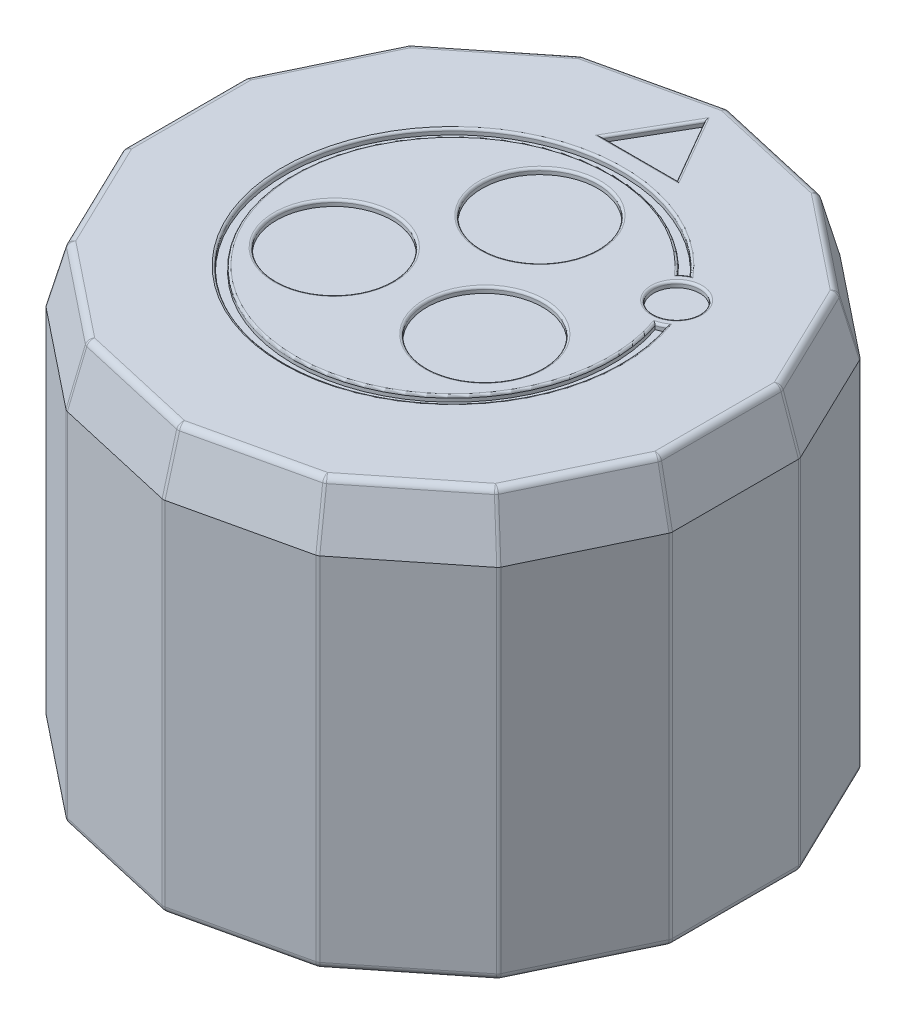
SolidWorks part; units mm, degrees
ref_plane "Front Plane" through (0, 0, 0) normal (0, 0, 1) x (1, 0, 0)
ref_plane "Top Plane" through (0, 0, 0) normal (0, 1, 0) x (1, 0, 0)
ref_plane "Right Plane" through (0, 0, 0) normal (1, 0, 0) x (0, 0, -1)
sketch "Sketch2" plane through (0, 0, 0) normal (0, 1, 0) x (1, 0, 0)
  line L1 (5.5103, -11.4423) -> (9.9293, -7.9183)
  line L2 (9.9293, -7.9183) -> (12.3816, -2.826)
  line L3 (12.3816, -2.826) -> (12.3816, 2.826)
  line L4 (12.3816, 2.826) -> (9.9293, 7.9183)
  line L5 (9.9293, 7.9183) -> (5.5103, 11.4423)
  line L6 (5.5103, 11.4423) -> (0, 12.7)
  line L7 (0, 12.7) -> (-5.5103, 11.4423)
  line L8 (-5.5103, 11.4423) -> (-9.9293, 7.9183)
  line L9 (-9.9293, 7.9183) -> (-12.3816, 2.826)
  line L10 (-12.3816, 2.826) -> (-12.3816, -2.826)
  line L11 (-12.3816, -2.826) -> (-9.9293, -7.9183)
  line L12 (-9.9293, -7.9183) -> (-5.5103, -11.4423)
  line L13 (-5.5103, -11.4423) -> (0, -12.7)
  line L14 (0, -12.7) -> (5.5103, -11.4423)
  circle A0 centre (0, 0) radius 12.7 construction
  dimension "D1" = 25.4
extrude "Boss-Extrude2" add sketch "Sketch2" along normal blind 2.54 draft 15
sketch "Sketch3" plane through (0, 0, 0) normal (0, -1, 0) x (1, 0, 0)
  line L0 (0, 10.0947) -> (-4.3799, 9.095)
  line L1 (0, 12.7) -> (-5.5103, 11.4423)
  line L2 (-5.5103, 11.4423) -> (-9.9293, 7.9183)
  line L3 (-9.9293, 7.9183) -> (-12.3816, 2.826)
  line L4 (-12.3816, 2.826) -> (-12.3816, -2.826)
  line L5 (-12.3816, -2.826) -> (-9.9293, -7.9183)
  line L6 (-9.9293, -7.9183) -> (-5.5103, -11.4423)
  line L7 (-5.5103, -11.4423) -> (0, -12.7)
  line L8 (0, -12.7) -> (5.5103, -11.4423)
  line L9 (5.5103, -11.4423) -> (9.9293, -7.9183)
  line L10 (9.9293, -7.9183) -> (12.3816, -2.826)
  line L11 (12.3816, -2.826) -> (12.3816, 2.826)
  line L12 (12.3816, 2.826) -> (9.9293, 7.9183)
  line L13 (9.9293, 7.9183) -> (5.5103, 11.4423)
  line L14 (5.5103, 11.4423) -> (0, 12.7)
  line L15 (-4.3799, 9.095) -> (-7.8923, 6.2939)
  line L16 (-7.8923, 6.2939) -> (-9.8416, 2.2463)
  line L17 (-9.8416, 2.2463) -> (-9.8416, -2.2463)
  line L18 (-9.8416, -2.2463) -> (-7.8923, -6.2939)
  line L19 (-7.8923, -6.2939) -> (-4.3799, -9.095)
  line L20 (-4.3799, -9.095) -> (0, -10.0947)
  line L21 (0, -10.0947) -> (4.3799, -9.095)
  line L22 (4.3799, -9.095) -> (7.8923, -6.2939)
  line L23 (7.8923, -6.2939) -> (9.8416, -2.2463)
  line L24 (9.8416, -2.2463) -> (9.8416, 2.2463)
  line L25 (9.8416, 2.2463) -> (7.8923, 6.2939)
  line L26 (7.8923, 6.2939) -> (4.3799, 9.095)
  line L27 (4.3799, 9.095) -> (0, 10.0947)
  line L28 (0, 0) -> (0, 3.7295) construction
  line L29 (0, 0) -> (-2.7063, -1.5625) construction
  line L30 (1.4494, 2.6266) -> (-2.9994, 0.0581)
  line L33 (-12.3816, -2.826) -> (-12.3816, 2.826) construction
  circle A0 centre (0, 0) radius 12.7 construction
  circle A1 centre (0, 0) radius 3 construction
  circle A2 centre (0, 0) radius 5.08
  circle A3 centre (0, 0) radius 3
  line M29 (5.5103, 11.4423) -> (0, 12.7)
  line M30 (0, 12.7) -> (-5.5103, 11.4423)
  line M31 (-5.5103, 11.4423) -> (-9.9293, 7.9183)
  line M32 (-9.9293, 7.9183) -> (-12.3816, 2.826)
  line M33 (-12.3816, 2.826) -> (-12.3816, -2.826)
  line M34 (-12.3816, -2.826) -> (-9.9293, -7.9183)
  line M35 (-9.9293, -7.9183) -> (-5.5103, -11.4423)
  line M36 (-5.5103, -11.4423) -> (0, -12.7)
  line M37 (0, -12.7) -> (5.5103, -11.4423)
  line M38 (5.5103, -11.4423) -> (9.9293, -7.9183)
  line M39 (9.9293, -7.9183) -> (12.3816, -2.826)
  line M40 (12.3816, -2.826) -> (12.3816, 2.826)
  line M41 (12.3816, 2.826) -> (9.9293, 7.9183)
  line M42 (9.9293, 7.9183) -> (5.5103, 11.4423)
  dimension "D1" = 25.4
  dimension "D3" = 6
  dimension "D4" = 60
  dimension "D6" = 10.16
  dimension "D5" = 1.55
  dimension "D2" = 2.54
extrude "Boss-Extrude3" add sketch "Sketch3" along normal blind 15.73 contours A2 A1 | L27 L26 L25 L24 L23 L22 L21 L20 L19 L18 L17 L16 L15 L0 M42 M29 M30 M31 M32 M33 M34 M35 M36 M37 M38 M39 M40 M41
sketch "Sketch5" plane through (0, 0, 0) normal (0, -1, 0) x (1, 0, 0)
  circle A0 centre (0, 0) radius 3.125
  dimension "D1" = 6.25
extrude "Cut-Extrude1" cut sketch "Sketch5" against normal blind 1.27
fillet "Fillet1" radius 1.905 15 edges at (0, 0, 5.08) (8.867, 0, 4.2701) (9.8416, 0, 0) (8.867, 0, -4.2701) (6.1361, 0, -7.6945) (2.19, 0, -9.5948) (-2.19, 0, -9.5948) (-6.1361, 0, -7.6945) (-8.867, 0, -4.2701) (-9.8416, 0, 0) (-8.867, 0, 4.2701) (-6.1361, 0, 7.6945) (-2.19, 0, 9.5948) (2.19, 0, 9.5948) (6.1361, 0, 7.6945)
fillet "Fillet2" radius 0.25 2 edges at (0, -15.73, -5.08) (0, -15.73, -3)
fillet "Fillet6" radius 0.3 42 edges at (10.5422, 2.54, 5.0769) (11.701, 2.54, 0) (10.5422, 2.54, -5.0769) (7.2955, 2.54, -9.1482) (2.6037, 2.54, -11.4076) (0, 1.27, 12.351) (-5.3589, 1.27, 11.1278) (-9.6564, 1.27, 7.7007) (-12.0413, 1.27, 2.7483) (-12.0413, 1.27, -2.7483) (-9.6564, 1.27, -7.7007) (-5.3589, 1.27, -11.1278) (0, 1.27, -12.351) (5.3589, 1.27, -11.1278) (9.6564, 1.27, -7.7007) (12.0413, 1.27, -2.7483) (12.0413, 1.27, 2.7483) (9.6564, 1.27, 7.7007) (5.3589, 1.27, 11.1278) (-2.6037, 2.54, -11.4076) (-7.2955, 2.54, -9.1482) (-10.5422, 2.54, -5.0769) (-11.701, 2.54, 0) (-10.5422, 2.54, 5.0769) (2.6037, 2.54, 11.4076) (-7.2955, 2.54, 9.1482) (-2.6037, 2.54, 11.4076) (9.9293, -7.865, 7.9183) (5.5103, -7.865, 11.4423) (0, -7.865, 12.7) (-5.5103, -7.865, 11.4423) (-9.9293, -7.865, 7.9183) (-12.3816, -7.865, 2.826) (-12.3816, -7.865, -2.826) (-9.9293, -7.865, -7.9183) (-5.5103, -7.865, -11.4423) (0, -7.865, -12.7) (5.5103, -7.865, -11.4423) (9.9293, -7.865, -7.9183) (12.3816, -7.865, -2.826) (7.2955, 2.54, 9.1482) (12.3816, -7.865, 2.826)
fillet "Fillet7" radius 0.3 42 edges at (-5.507, -15.73, 11.4354) (-2.7552, -15.73, 12.0712) (0, -15.73, 12.6923) (2.7552, -15.73, 12.0712) (5.507, -15.73, 11.4354) (7.7198, -15.73, 9.6803) (9.9232, -15.73, 7.9135) (11.1554, -15.73, 5.3722) (12.3741, -15.73, 2.8243) (12.3816, -15.73, 0) (12.3741, -15.73, -2.8243) (11.1554, -15.73, -5.3722) (9.9232, -15.73, -7.9135) (7.7198, -15.73, -9.6803) (5.507, -15.73, -11.4354) (2.7552, -15.73, -12.0712) (0, -15.73, -12.6923) (-2.7552, -15.73, -12.0712) (-5.507, -15.73, -11.4354) (-7.7198, -15.73, -9.6803) (-9.9232, -15.73, -7.9135) (-11.1554, -15.73, -5.3722) (-12.3741, -15.73, -2.8243) (-12.3816, -15.73, 0) (-12.3741, -15.73, 2.8243) (-11.1554, -15.73, 5.3722) (-9.9232, -15.73, 7.9135) (-7.7198, -15.73, 9.6803) (-2.19, -15.73, 9.5948) (-6.1361, -15.73, 7.6945) (-8.867, -15.73, 4.2701) (-9.8416, -15.73, 0) (-8.867, -15.73, -4.2701) (-6.1361, -15.73, -7.6945) (-2.19, -15.73, -9.5948) (2.19, -15.73, -9.5948) (6.1361, -15.73, -7.6945) (8.867, -15.73, -4.2701) (9.8416, -15.73, 0) (8.867, -15.73, 4.2701) (6.1361, -15.73, 7.6945) (2.19, -15.73, 9.5948)
sketch "Sketch6" plane through (0, 2.54, 0) normal (0, 1, 0) x (1, 0, 0)
  line L0 (0, 0) -> (6.2142, 3.5877) construction
  line L1 (3.2996, -1.905) -> (0, 3.81) construction
  line L2 (0, 3.81) -> (-3.2996, -1.905) construction
  line L3 (-3.2996, -1.905) -> (3.2996, -1.905) construction
  circle A0 centre (0, 0) radius 1.905 construction
  circle A1 centre (0, 3.81) radius 2.54
  circle A2 centre (3.2996, -1.905) radius 2.54
  circle A3 centre (-3.2996, -1.905) radius 2.54
  circle A4 centre (0, 0) radius 6.985
  circle A5 centre (0, 0) radius 7.366
  circle A6 centre (6.2142, 3.5877) radius 1.016
  circle A7 centre (6.2142, 3.5877) radius 1.397
  dimension "D1" = 3.81
  dimension "D2" = 5.08
  dimension "D3" = 5.08
  dimension "D4" = 5.08
  dimension "D5" = 13.97
  dimension "D8" = 2.032
  dimension "D7" = 7.1755
  dimension "D6" = 0.381
  dimension "D9" = 0.381
extrude "Cut-Extrude2" cut sketch "Sketch6" against normal blind 0.25 contours A7 A4 A5 | A5 A6 | A4 A6 A5 | A4 A6 | A1 | A2 | A3
fillet "Fillet8" radius 0.1 8 edges at (6.7927, 2.54, -2.3162) (5.4022, 2.54, -4.7246) (-6.3791, 2.54, 3.683) (-6.0492, 2.54, 3.4925) (6.2142, 2.54, -2.5717) (0, 2.54, -1.27) (3.2996, 2.54, 4.445) (-3.2996, 2.54, 4.445)
sketch "Sketch7" plane through (0, 2.54, 0) normal (0, 1, 0) x (1, 0, 0)
  line L0 (0, 0) -> (0, 14.1515) construction
  line L2 (1.6498, 8.1732) -> (0, 11.0307)
  line L3 (0, 11.0307) -> (-1.6498, 8.1732)
  line L4 (-1.6498, 8.1732) -> (1.6498, 8.1732)
  circle A0 centre (0, 9.1257) radius 0.9525 construction
  dimension "D1" = 1.905
  dimension "D2" = 7.5491
  dimension "D3" = 19.939
extrude "Cut-Extrude3" cut sketch "Sketch7" against normal blind 0.25
fillet "Fillet9" radius 0.1 3 edges at (0.8249, 2.54, -9.602) (-0.8249, 2.54, -9.602) (0, 2.54, -8.1732)
sketch "Sketch8" plane through (0, 1.27, 0) normal (0, -1, 0) x (1, 0, 0)
  line L0 (0, 0) -> (1.936, 0) construction
  line L1 (-2.7135, 1.55) -> (2.7135, 1.55)
  circle A0 centre (0, 0) radius 3.125
  circle M4 centre (0, 0) radius 3.125
  dimension "D1" = 6.25
  dimension "D2" = 1.55
extrude "Boss-Extrude4" add sketch "Sketch8" along normal blind 9 contours L1 M4
